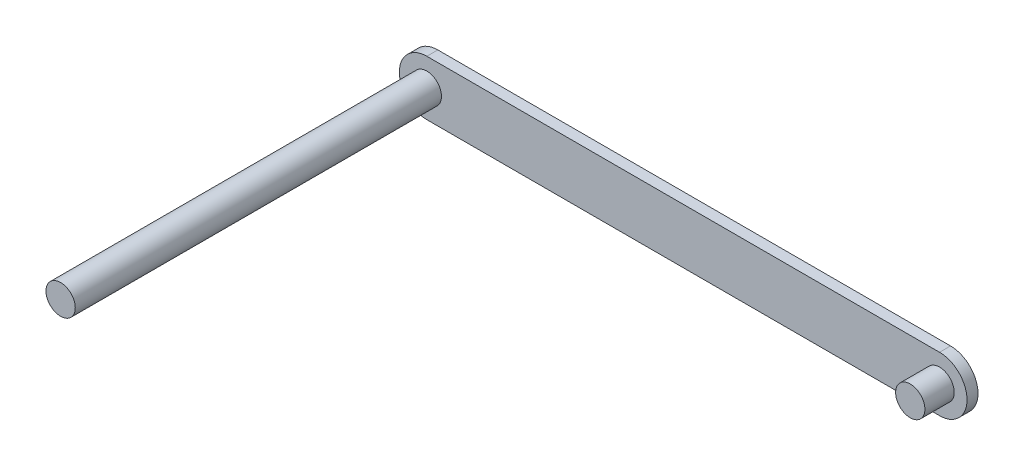
SolidWorks part; units mm, degrees
material "PBT General Purpose"
ref_plane "Front Plane" through (0, 0, 0) normal (0, 0, 1) x (1, 0, 0)
ref_plane "Top Plane" through (0, 0, 0) normal (0, 1, 0) x (1, 0, 0)
ref_plane "Right Plane" through (0, 0, 0) normal (1, 0, 0) x (0, 0, -1)
sketch "Sketch1" plane through (0, 0, 0) normal (0, 0, 1) x (1, 0, 0)
  line L0 (0, 7.5) -> (140, 7.5)
  line L6 (0, -7.5) -> (140, -7.5)
  arc A2 (0, 7.5) -> (0, -7.5) centre (0, 0) ccw
  arc A3 (140, -7.5) -> (140, 7.5) centre (140, 0) ccw
  dimension "D1" = 15
  dimension "D2" = 140
extrude "Boss-Extrude1" add sketch "Sketch1" along normal blind 3
sketch "Sketch2" plane through (0, 0, 3) normal (0, 0, 1) x (1, 0, 0)
  circle A0 centre (0, 0) radius 4
  circle A1 centre (140, 0) radius 4
  dimension "D1" = 8
  dimension "D2" = 140
extrude "Boss-Extrude2" add sketch "Sketch2" along normal blind 8
sketch "Sketch3" plane through (0, 0, 11) normal (0, 0, 1) x (1, 0, 0)
  circle A0 centre (0, 0) radius 4 construction
  circle A1 centre (0, 0) radius 4
extrude "Boss-Extrude3" add sketch "Sketch3" along normal blind 92
